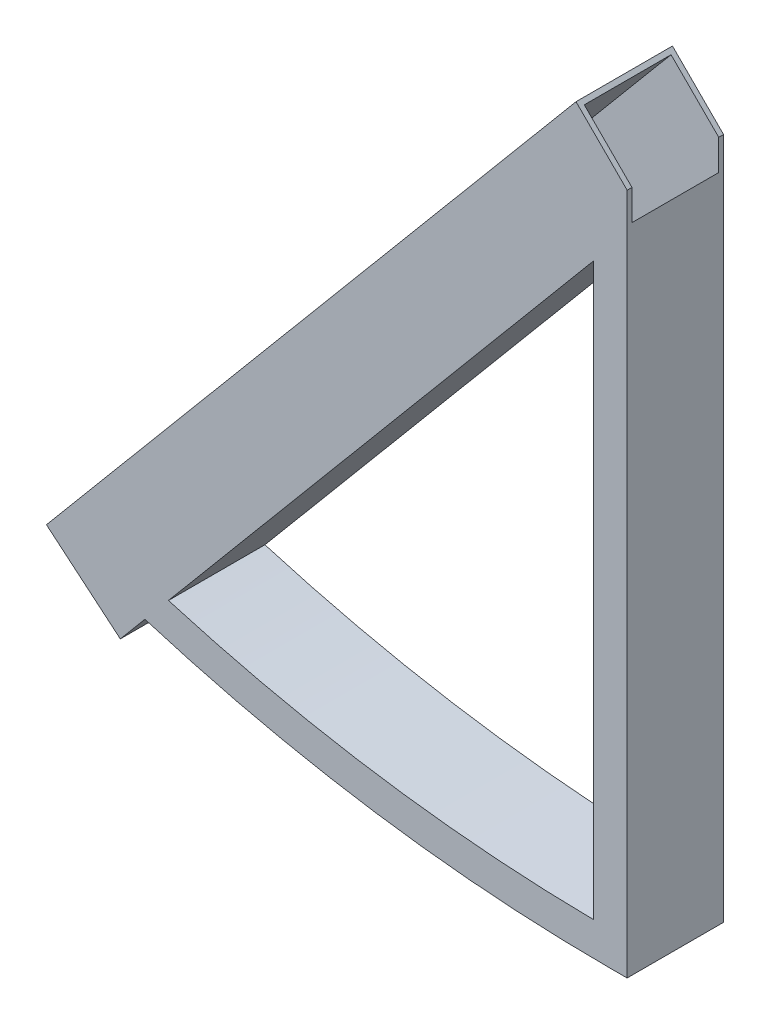
SolidWorks part; units mm, degrees
ref_plane "Front Plane" through (0, 0, 0) normal (0, 0, 1) x (1, 0, 0)
ref_plane "Top Plane" through (0, 0, 0) normal (0, 1, 0) x (1, 0, 0)
ref_plane "Right Plane" through (0, 0, 0) normal (1, 0, 0) x (0, 0, -1)
sketch "Sketch1" plane through (0, 0, 0) normal (0, 0, 1) x (1, 0, 0)
  line L0 (-3.5, 7) -> (-3.5, 125.2716)
  line L1 (0, 0) -> (145, 0) construction
  line L2 (145, 0) -> (0, 145) construction
  line L3 (0, 145) -> (-109.2739, 14.7724) construction
  line L5 (-7.0981, 152.0981) -> (-116.9343, 21.2003)
  line L6 (-116.9343, 21.2003) -> (-101.6134, 8.3446)
  line L7 (-101.6134, 8.3446) -> (-96.5092, 14.4276)
  line L9 (3.5, 141.5) -> (3.5, 0)
  line L10 (3.5, 0) -> (0, 0)
  line L11 (-91.625, 20.2483) -> (-3.5, 125.2716)
  line L13 (-3.5, 125.2716) -> (-18.8209, 138.1274) construction
  line L14 (3.5, 141.5) -> (-7.0981, 152.0981)
  line L15 (-3.5, 7) -> (3.5, 7) construction
  line L16 (0, 7) -> (0, 0) construction
  line L17 (3.5, 0) -> (-3.5, 0) construction
  line L18 (-3.5, 0) -> (-3.5, 7) construction
  arc A0 (0, 0) -> (-96.5092, 14.4276) centre (0, 330) cw
  arc A1 (-91.625, 20.2483) -> (-3.5, 7) centre (0, 330) ccw
  dimension "D2" = 330
  dimension "D1" = 145
  dimension "D3" = 50
  dimension "D4" = 20
  dimension "D6" = 45
  dimension "D7" = 7
  dimension "D8" = 145
  dimension "D9" = 170
extrude "Boss-Extrude1" add sketch "Sketch1" along normal blind 10 and the other way blind 10
sketch "Sketch2" plane through (-37.8753, -45.1381, 0) normal (-0.6428, -0.766, 0) x (-0.766, 0.6428, 0)
  line L0 (103.2042, -10) -> (83.2042, 10) construction
  line L1 (83.2042, -10) -> (103.2042, 10) construction
  line L3 (102.2042, 9) -> (84.2042, 9)
  line L4 (83.2042, 10) -> (83.2042, -10)
  line L5 (83.2042, -10) -> (103.2042, -10)
  line L6 (103.2042, -10) -> (103.2042, 10)
  line L7 (103.2042, 10) -> (83.2042, 10)
  line L8 (83.2042, 10) -> (83.2042, -10) construction
  line L9 (83.2042, -10) -> (103.2042, -10) construction
  line L10 (103.2042, -10) -> (103.2042, 10) construction
  line L11 (103.2042, 10) -> (83.2042, 10) construction
  line L12 (102.2042, 9) -> (102.2042, -9)
  line L13 (102.2042, -9) -> (84.2042, -9)
  line L14 (84.2042, 9) -> (84.2042, -9)
  line L15 (102.2042, 9) -> (84.2042, -9) construction
  line L16 (102.2042, -9) -> (84.2042, 9) construction
  point P2 (93.2042, 0)
  point P9 (88.0419, 5.1623)
  dimension "D2" = 18
  dimension "D1" = 0
extrude "Cut-Extrude1" cut sketch "Sketch2" against normal through all both and the other way through all
